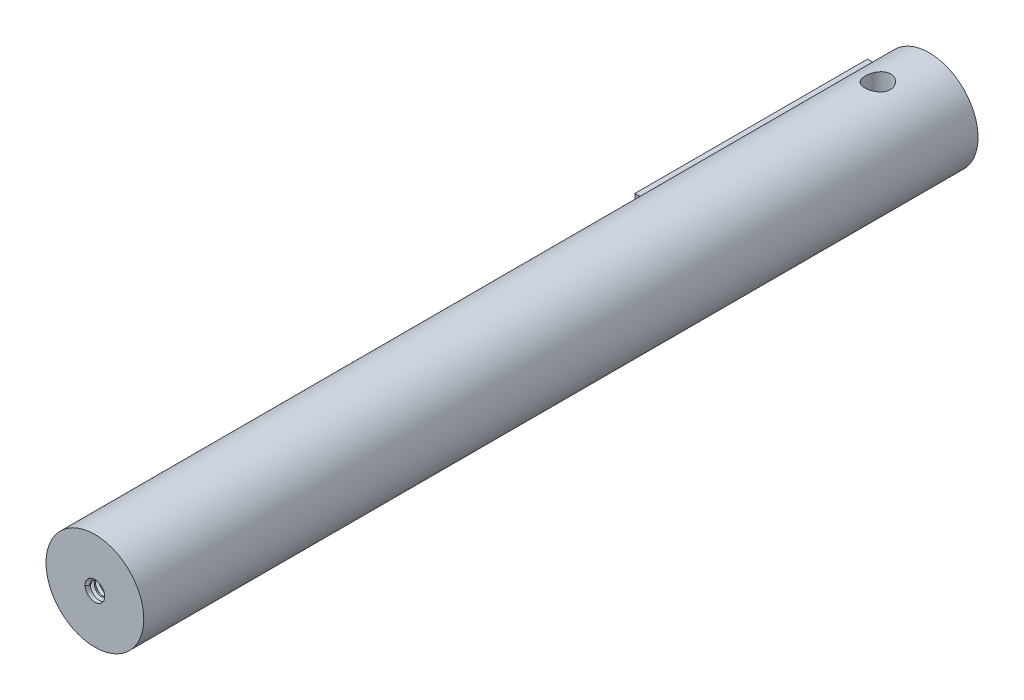
SolidWorks part; units mm, degrees
material "Cast Carbon Steel"
ref_plane "Front Plane" through (0, 0, 0) normal (0, 0, 1) x (1, 0, 0)
ref_plane "Top Plane" through (0, 0, 0) normal (0, 1, 0) x (1, 0, 0)
ref_plane "Right Plane" through (0, 0, 0) normal (1, 0, 0) x (0, 0, -1)
sketch "Sketch1" plane through (0, 0, 0) normal (0, 0, 1) x (1, 0, 0)
  line L0 (0, 0) -> (0, 3.175)
  line L1 (0, 3.175) -> (-15.621, 3.175)
  line L2 (-15.621, 3.175) -> (-15.621, -2.921)
  line L3 (-15.621, -2.921) -> (0, -2.921)
  line L4 (0, -2.921) -> (0, 0)
  circle A0 centre (0, 0) radius 12.3825
  dimension "D1" = 24.765
  dimension "D2" = 6.096
  dimension "D3" = 3.175
  dimension "D4" = 15.621
extrude "Boss-Extrude4" add sketch "Sketch1" along normal blind 58.928 contours L3 A0 L1 L0 L4 | L1 A0 L3 L4 L0 | A0 L1 L2 L3 region at (-6.1283, 0.1244, 0) region at (1.125, -0.0228, 0) region at (-13.9364, 0.1366, 0)
sketch "Sketch8" plane through (0, 0, 58.928) normal (0, 0, 1) x (1, 0, 0)
  circle A0 centre (0, 0) radius 12.3825
  dimension "D1" = 24.765
extrude "Boss-Extrude5" add sketch "Sketch8" along normal blind 152.4
sketch "Sketch10" plane through (0, 0, 211.328) normal (0, 0, 1) x (1, 0, 0)
  circle A0 centre (0, 0) radius 2.4876
  dimension "D1" = 4.9752
extrude "Cut-Extrude1" cut sketch "Sketch10" against normal blind 12.7
thread "Thread1" pitch 1.27 method extrude profile "Thread Profile1" start angle 0, offset 0, length 0, pitch 1.27, diameter 4.9752
ref_plane "Plane1" through (-2.4876, 0, 211.328) normal (0, -1, 0) x (-1, 0, 0)
sketch "Thread Profile1" plane through (-2.4876, 0, 211.328) normal (0, -1, 0) x (-1, 0, 0)
  line L0 (0, 0) -> (0, 1.27) construction
  line L11 (0, 0) -> (0, 1.1112)
  line L12 (0, 1.1112) -> (-0.6874, 0.7144)
  line L13 (-0.6874, 0.7144) -> (-0.6874, 0.3969)
  line L15 (-0.6874, 0.3969) -> (0, 0)
  line L17 (-0.6874, 0.5556) -> (0, 0.5556) construction
  point P2 (0, 0)
  dimension "Pitch" = 1.27
  dimension "Profile_Angle" = 60
  dimension "Profile_Land" = 0.3175
  dimension "Profile_Height" = 0.6874
sketch "Sketch11" plane through (0, 0, 0) normal (0, 1, 0) x (1, 0, 0)
  line L0 (12.3825, 0) -> (-12.033, 0) construction
  line L1 (12.3825, -211.328) -> (12.3825, 0) construction
  circle A0 centre (-0.3175, -12.7) radius 3.175
  dimension "D1" = 6.35
  dimension "D2" = 12.7
  dimension "D3" = 12.7
extrude "Cut-Extrude2" cut sketch "Sketch11" against normal through all and the other way through all
